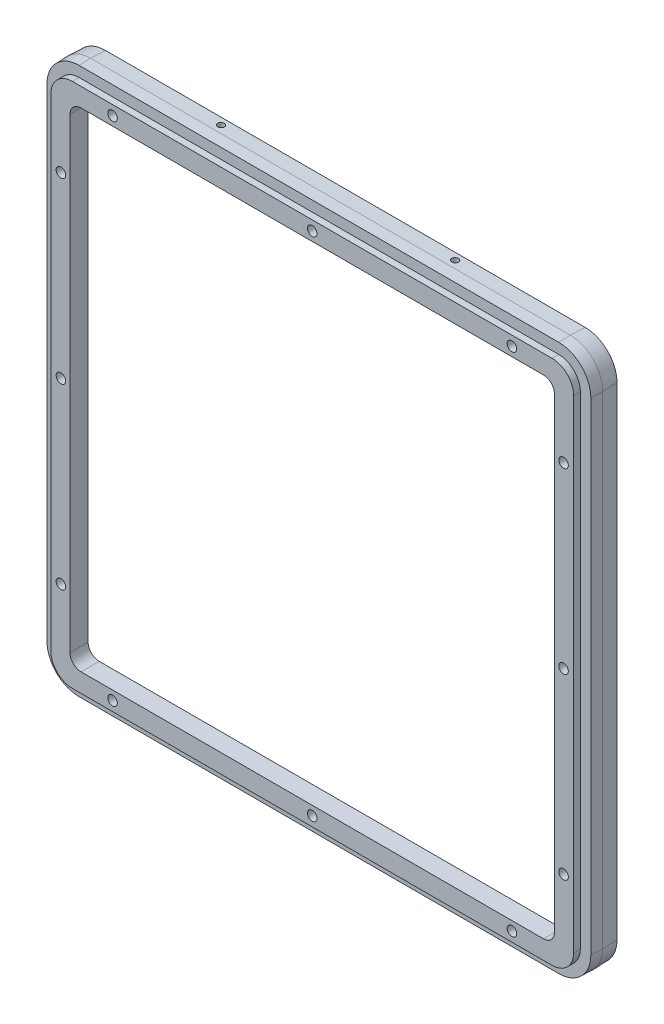
SolidWorks part; units mm, degrees
note: The reader was unsure of these and kept them because the rebuilt part matched: shared geometry of "Sketch4<4>", "Sketch5<4>", "Sketch6<3>".
ref_plane "Front Plane" through (0, 0, 0) normal (0, 0, 1) x (1, 0, 0)
ref_plane "Top Plane" through (0, 0, 0) normal (0, 1, 0) x (1, 0, 0)
ref_plane "Right Plane" through (0, 0, 0) normal (1, 0, 0) x (0, 0, -1)
sketch "Sketch1" plane through (0, 0, 0) normal (0, 0, 1) x (1, 0, 0)
  line L1 (-127.508, -145.542) -> (127.508, -145.542)
  line L2 (-144.78, -128.27) -> (-144.78, 128.27)
  line L3 (-127.508, 145.542) -> (127.508, 145.542)
  line L4 (144.78, -128.27) -> (144.78, 128.27)
  line L5 (-144.78, -145.542) -> (144.78, 145.542) construction
  line L6 (-144.78, 145.542) -> (144.78, -145.542) construction
  arc A0 (127.508, 145.542) -> (144.78, 128.27) centre (127.508, 128.27) cw
  arc A1 (127.508, -145.542) -> (144.78, -128.27) centre (127.508, -128.27) ccw
  arc A2 (-127.508, -145.542) -> (-144.78, -128.27) centre (-127.508, -128.27) cw
  arc A3 (-144.78, 128.27) -> (-127.508, 145.542) centre (-127.508, 128.27) cw
  point P0 (0, 0)
  dimension "D3" = 17.272
  dimension "D1" = 289.56
  dimension "D2" = 291.084
extrude "Boss-Extrude1" add sketch "Sketch1" along normal blind 6.096 draft 2 and the other way blind 7.874 draft 2 contours L1 A1 L4 A0 L3 A3 L2 A2
sketch "Sketch4" plane through (0, 0, 0) normal (0, 0, 1) x (1, 0, 0)
  line L0 (-45.6452, 0) -> (45.6452, 0) construction
  line L1 (0, 128.733) -> (0, -128.733) construction
  line L2 (-122.936, -129.794) -> (122.936, -129.794)
  line L3 (-128.778, -123.952) -> (-128.778, 123.952)
  line L8 (-122.936, 129.794) -> (122.936, 129.794)
  line L9 (128.778, -123.952) -> (128.778, 123.952)
  line L10 (-128.778, -129.794) -> (128.778, 129.794) construction
  line L11 (-128.778, 129.794) -> (128.778, -129.794) construction
  circle A17 centre (-106.172, -134.62) radius 2.54
  circle A18 centre (-133.604, -94.742) radius 2.54
  circle A19 centre (133.604, 0) radius 2.54
  circle A20 centre (133.604, -94.742) radius 2.54
  circle A21 centre (106.172, -134.62) radius 2.54
  circle A22 centre (106.172, 134.62) radius 2.54
  circle A23 centre (133.604, 94.742) radius 2.54
  circle A24 centre (-133.604, 94.742) radius 2.54
  circle A25 centre (-106.172, 134.62) radius 2.54
  arc A26 (122.936, 129.794) -> (128.778, 123.952) centre (122.936, 123.952) cw
  arc A27 (122.936, -129.794) -> (128.778, -123.952) centre (122.936, -123.952) ccw
  arc A28 (-122.936, -129.794) -> (-128.778, -123.952) centre (-122.936, -123.952) cw
  arc A29 (-128.778, 123.952) -> (-122.936, 129.794) centre (-122.936, 123.952) cw
  circle A30 centre (0, 134.62) radius 2.54
  circle A31 centre (0, -134.62) radius 2.54
  circle A32 centre (-133.604, 0) radius 2.54
  point P26 (0, 0)
  dimension "D2" = 134.62
  dimension "D8" = 245.872
  dimension "D6" = 2.286
  dimension "D1" = 5.08
  dimension "D7" = 5.842
  dimension "D3" = 27.432
  dimension "D4" = 39.878
  dimension "D5" = 259.588
extrude "Cut-Extrude1" cut sketch "Sketch4" against normal through all both and the other way through all contours A29 L3 A28 L2 A27 L9 A26 L8
sketch "Sketch5" plane through (0, 0, 0) normal (0, 0, 1) x (1, 0, 0)
  line L12 (122.936, 129.794) -> (-122.936, 129.794) construction
  line L13 (-122.936, -129.794) -> (122.936, -129.794) construction
  line L14 (128.778, -123.952) -> (128.778, 123.952) construction
  line L15 (-128.778, 123.952) -> (-128.778, -123.952) construction
  line L16 (-127.508, -139.7411) -> (127.508, -139.7411)
  line L17 (138.9791, -128.27) -> (138.9791, 128.27)
  line L18 (127.508, 139.7411) -> (-127.508, 139.7411)
  line L19 (-138.9791, 128.27) -> (-138.9791, -128.27)
  line L20 (-127.508, -145.3291) -> (127.508, -145.3291)
  line L21 (144.5671, -128.27) -> (144.5671, 128.27)
  line L22 (127.508, 145.3291) -> (-127.508, 145.3291)
  line L23 (-144.5671, 128.27) -> (-144.5671, -128.27)
  line L24 (-127.508, -145.3291) -> (127.508, -145.3291)
  line L25 (144.5671, -128.27) -> (144.5671, 128.27)
  line L26 (127.508, 145.3291) -> (-127.508, 145.3291)
  line L27 (-144.5671, 128.27) -> (-144.5671, -128.27)
  line L28 (-122.936, -129.794) -> (122.936, -129.794)
  line L29 (128.778, -123.952) -> (128.778, 123.952)
  line L30 (-128.778, 123.952) -> (-128.778, -123.952)
  line L31 (122.936, 129.794) -> (-122.936, 129.794)
  arc A15 (-122.936, 129.794) -> (-128.778, 123.952) centre (-122.936, 123.952) ccw construction
  arc A19 (127.508, -139.7411) -> (138.9791, -128.27) centre (127.508, -128.27) ccw
  arc A20 (138.9791, 128.27) -> (127.508, 139.7411) centre (127.508, 128.27) ccw
  arc A21 (-127.508, 139.7411) -> (-138.9791, 128.27) centre (-127.508, 128.27) ccw
  arc A22 (-138.9791, -128.27) -> (-127.508, -139.7411) centre (-127.508, -128.27) ccw
  arc A23 (-144.5671, -128.27) -> (-127.508, -145.3291) centre (-127.508, -128.27) ccw
  arc A24 (127.508, -145.3291) -> (144.5671, -128.27) centre (127.508, -128.27) ccw
  arc A25 (144.5671, 128.27) -> (127.508, 145.3291) centre (127.508, 128.27) ccw
  arc A26 (-127.508, 145.3291) -> (-144.5671, 128.27) centre (-127.508, 128.27) ccw
  arc A27 (-144.5671, -128.27) -> (-127.508, -145.3291) centre (-127.508, -128.27) ccw
  arc A28 (127.508, -145.3291) -> (144.5671, -128.27) centre (127.508, -128.27) ccw
  arc A29 (144.5671, 128.27) -> (127.508, 145.3291) centre (127.508, 128.27) ccw
  arc A30 (-127.508, 145.3291) -> (-144.5671, 128.27) centre (-127.508, 128.27) ccw
  arc A32 (122.936, -129.794) -> (128.778, -123.952) centre (122.936, -123.952) ccw construction
  arc A33 (-128.778, -123.952) -> (-122.936, -129.794) centre (-122.936, -123.952) ccw construction
  arc A34 (128.778, 123.952) -> (122.936, 129.794) centre (122.936, 123.952) ccw construction
  arc A35 (122.936, -129.794) -> (128.778, -123.952) centre (122.936, -123.952) ccw
  arc A36 (-128.778, -123.952) -> (-122.936, -129.794) centre (-122.936, -123.952) ccw
  arc A37 (128.778, 123.952) -> (122.936, 129.794) centre (122.936, 123.952) ccw
  arc A38 (-122.936, 129.794) -> (-128.778, 123.952) centre (-122.936, 123.952) ccw
  dimension "D1" = 0
  dimension "D3" = 256.54
  dimension "D2" = 5.588
extrude "Boss-Extrude2" add sketch "Sketch5" along normal blind 3.556 from surface at 6.096 contours L19 A22 L16 A19 L17 A20 L18 A21 A38 L31 A37 L29 A35 L28 A36 L30 starting at face at (0, 0, 6.096)
extrude "Cut-Extrude2" cut sketch "Sketch4<4>" against normal through all both and the other way through all
sketch "Sketch4<4>" plane through (0, 0, 0) normal (0, 0, 1) x (1, 0, 0) same geometry as "Sketch4"
extrude "Cut-Extrude5" cut sketch "Sketch5<4>" along normal blind 7.874 from surface at -7.874 contours L19 A22 L16 A19 L17 A20 L18 A21 A38 L31 A37 L29 A35 L28 A36 L30 starting at face at (103.632, -134.62, -7.874)
sketch "Sketch5<4>" plane through (0, 0, 0) normal (0, 0, 1) x (1, 0, 0) same geometry as "Sketch5"
sketch "Sketch6" plane through (0, 0, 0) normal (0, 1, 0) x (1, 0, 0)
  line L0 (-57.15, 2.794) -> (-44.45, 2.794)
  line L1 (-57.15, 2.794) -> (-57.15, 7.874)
  line L2 (-57.15, 7.874) -> (-44.45, 7.874)
  line L3 (-44.45, 2.794) -> (-44.45, 7.874)
  line L4 (0, 57.3702) -> (0, -21.3919) construction
  line L5 (-127.508, 7.874) -> (127.508, 7.874) construction
  line L6 (44.45, 2.794) -> (44.45, 7.874)
  line L7 (57.15, 7.874) -> (44.45, 7.874)
  line L8 (57.15, 2.794) -> (57.15, 7.874)
  line L9 (57.15, 2.794) -> (44.45, 2.794)
  circle A0 centre (-72.39, 4.064) radius 1.778
  circle A1 centre (-62.23, 4.064) radius 1.778
  circle A2 centre (62.23, 4.064) radius 1.778
  circle A3 centre (72.39, 4.064) radius 1.778
  dimension "D3" = 3.556
  dimension "D7" = 2.032
  dimension "D1" = 12.7
  dimension "D2" = 5.08
  dimension "D4" = 10.16
  dimension "D5" = 44.45
  dimension "D6" = 72.39
extrude "Cut-Extrude6" cut sketch "Sketch6" against normal blind 160.02 contours L0 L3 L2 L1 | L7 L6 L9 L8 | A0 | A3
extrude "Cut-Extrude7" cut sketch "Sketch6<3>" along normal blind 160.02 contours A2 | A1
sketch "Sketch6<3>" plane through (0, 0, 0) normal (0, 1, 0) x (1, 0, 0) same geometry as "Sketch6"
